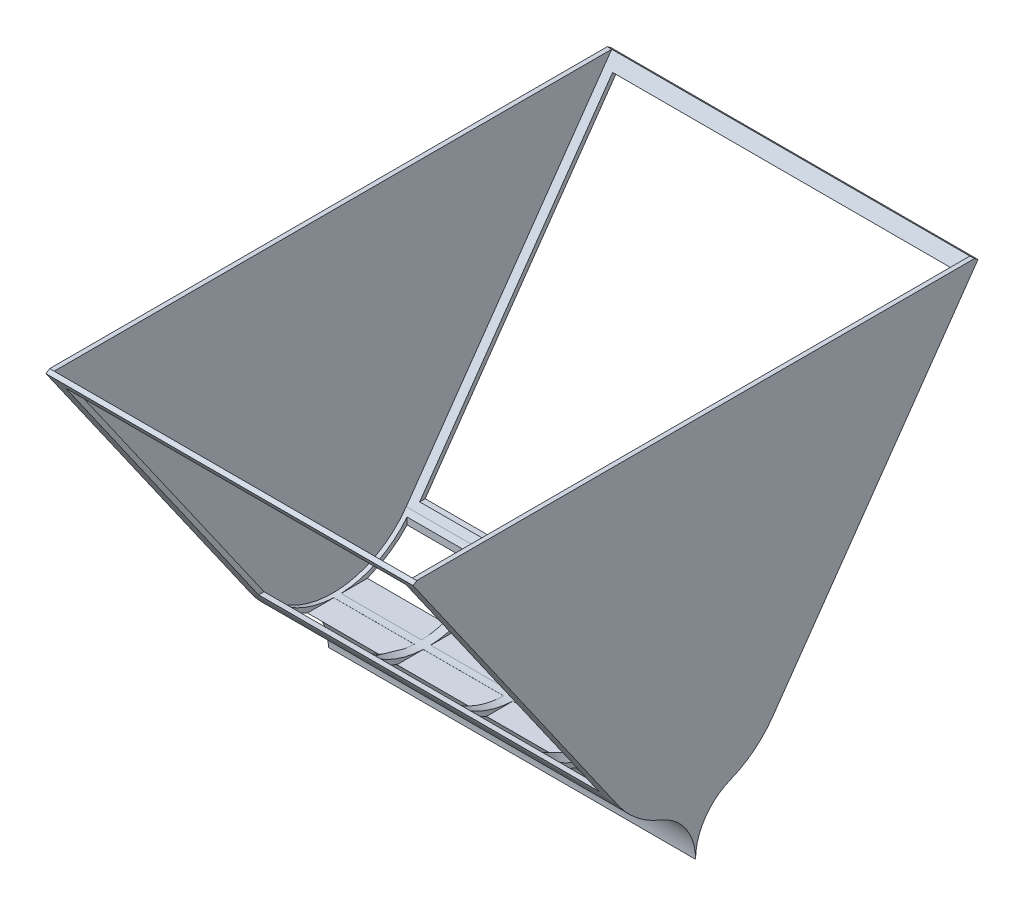
SolidWorks part; units mm, degrees
note: The reader was unsure of these and kept them because the rebuilt part matched: shared geometry of "Sketch4<3>".
ref_plane "Front Plane" through (0, 0, 0) normal (0, 0, 1) x (1, 0, 0)
ref_plane "Top Plane" through (0, 0, 0) normal (0, 1, 0) x (1, 0, 0)
ref_plane "Right Plane" through (0, 0, 0) normal (1, 0, 0) x (0, 0, -1)
sketch "Sketch1" plane through (0, 0, 0) normal (1, 0, 0) x (0, 0, -1)
  line L0 (-16.383, -11.4715) -> (-62.2692, 54.0606)
  line L1 (16.383, -11.4715) -> (62.2692, 54.0606)
  line L2 (-17.2022, -12.0451) -> (-63.0883, 53.4871)
  line L3 (17.2022, -12.0451) -> (63.0883, 53.4871)
  line L4 (0, -21) -> (0, -31) construction
  line L5 (16.383, -11.4715) -> (62.2692, 54.0606) construction
  line L6 (-62.2692, 54.0606) -> (-63.0883, 53.4871)
  line L7 (62.2692, 54.0606) -> (63.0883, 53.4871)
  arc A0 (-16.383, -11.4715) -> (16.383, -11.4715) centre (0, 0) ccw
  arc A1 (-17.2022, -12.0451) -> (17.2022, -12.0451) centre (0, 0) ccw
  arc A2 (7.7889, -19.5021) -> (0, -31) centre (12.381, -31) ccw
  arc A3 (0, -31) -> (-7.7889, -19.5021) centre (-12.381, -31) ccw
  dimension "D3" = 20
  dimension "D2" = 10
  dimension "D4" = 80
  dimension "D5" = 70
  dimension "D1" = 1
extrude "Boss-Extrude1" add sketch "Sketch1" along normal blind 80 contours L2 A1 L3 L7 L1 A0 L0 L6 | A3 A2 A1
sketch "Sketch2" plane through (0, 0, 0) normal (0, 0, 1) x (1, 0, 0)
  line L0 (78, 51.4871) -> (2, 51.4871)
  line L1 (2, 51.4871) -> (2, -10.0451)
  line L2 (2, -10.0451) -> (78, -10.0451)
  line L3 (78, -10.0451) -> (78, 51.4871)
  line L4 (0, 53.4871) -> (0, -12.0451)
  line L5 (80, 53.4871) -> (0, 53.4871)
  line L6 (80, -12.0451) -> (80, 53.4871)
  line L7 (0, -12.0451) -> (80, -12.0451)
  line L8 (0, 53.4871) -> (0, -12.0451)
  line L9 (80, 53.4871) -> (0, 53.4871)
  line L10 (80, -12.0451) -> (80, 53.4871)
  line L11 (0, -12.0451) -> (80, -12.0451)
  line L12 (0, -12.0451) -> (0, -19.5021)
  line L13 (80, -12.0451) -> (0, -12.0451)
  line L14 (80, -19.5021) -> (80, -12.0451)
  line L15 (0, -19.5021) -> (80, -19.5021)
  line L16 (0, -12.0451) -> (0, -19.5021)
  line L17 (80, -12.0451) -> (0, -12.0451)
  line L18 (80, -19.5021) -> (80, -12.0451)
  line L19 (0, -19.5021) -> (80, -19.5021)
  dimension "D1" = 0
  dimension "D2" = 0
  dimension "D3" = 2
extrude "Cut-Extrude1" cut sketch "Sketch2" against normal through all both and the other way through all contours L2 L3 L0 L1
sketch "Sketch3" plane through (0, 0, 0) normal (0, 1, 0) x (1, 0, 0)
  line L0 (80, 0) -> (0, 0) construction
  line L1 (80, 0) -> (0, 0)
  line L2 (40, -16.383) -> (40, 16.383)
  line L3 (40, 16.383) -> (0, -16.383)
  line L4 (0, 16.383) -> (0, -16.383)
  line L5 (0, -16.383) -> (80, -16.383)
  line L6 (80, -16.383) -> (80, 16.383)
  line L7 (80, 16.383) -> (0, 16.383)
  line L8 (0, 16.383) -> (0, -16.383)
  line L9 (0, -16.383) -> (80, -16.383)
  line L10 (80, -16.383) -> (80, 16.383)
  line L11 (80, 16.383) -> (0, 16.383)
  line L12 (0, 16.383) -> (40, -16.383)
  line L13 (40, -16.383) -> (80, 16.383)
  line L14 (0, 7.7889) -> (0, 0)
  line L15 (80, 7.7889) -> (0, 7.7889)
  line L16 (80, 0) -> (80, 7.7889)
  line L17 (0, 0) -> (80, 0)
  line L18 (0, 7.7889) -> (0, 0)
  line L19 (80, 7.7889) -> (0, 7.7889)
  line L20 (80, 0) -> (80, 7.7889)
  line L21 (0, 0) -> (80, 0)
  line L22 (0, 0) -> (0, -7.7889)
  line L23 (80, 0) -> (0, 0)
  line L24 (80, -7.7889) -> (80, 0)
  line L25 (0, -7.7889) -> (80, -7.7889)
  line L26 (0, 0) -> (0, -7.7889)
  line L27 (80, 0) -> (0, 0)
  line L28 (80, -7.7889) -> (80, 0)
  line L29 (0, -7.7889) -> (80, -7.7889)
  line L30 (40, 16.383) -> (80, -16.383)
  line L31 (60, 0) -> (60, -16.383)
  line L32 (60, -16.383) -> (60, 16.383)
  line L33 (20, 0) -> (20, 16.383)
  line L34 (20, 16.383) -> (20, -16.383)
  line L36 (1, -15.5639) -> (19, -15.5639)
  line L37 (1, -15.5639) -> (1, -0.8192)
  line L38 (1, -0.8192) -> (19, -0.8192)
  line L39 (19, -15.5639) -> (19, -0.8192)
  line L40 (1, 15.5639) -> (19, 15.5639)
  line L41 (1, 15.5639) -> (1, 0.8192)
  line L42 (1, 0.8192) -> (19, 0.8192)
  line L43 (19, 15.5639) -> (19, 0.8192)
  line L44 (21, 15.5639) -> (39, 15.5639)
  line L45 (21, 15.5639) -> (21, 0.8192)
  line L46 (21, 0.8192) -> (39, 0.8192)
  line L47 (39, 15.5639) -> (39, 0.8192)
  line L48 (21, -15.5639) -> (39, -15.5639)
  line L49 (21, -15.5639) -> (21, -0.8192)
  line L50 (21, -0.8192) -> (39, -0.8192)
  line L51 (39, -15.5639) -> (39, -0.8192)
  line L52 (41, -15.5639) -> (59, -15.5639)
  line L53 (41, -15.5639) -> (41, -0.8192)
  line L54 (41, -0.8192) -> (59, -0.8192)
  line L55 (59, -15.5639) -> (59, -0.8192)
  line L56 (41, 0.8192) -> (59, 0.8192)
  line L57 (41, 0.8192) -> (41, 15.5639)
  line L58 (41, 15.5639) -> (59, 15.5639)
  line L59 (59, 0.8192) -> (59, 15.5639)
  line L60 (61, -15.5639) -> (79, -15.5639)
  line L61 (61, -15.5639) -> (61, -0.8192)
  line L62 (61, -0.8192) -> (79, -0.8192)
  line L63 (79, -15.5639) -> (79, -0.8192)
  line L64 (61, 0.8192) -> (79, 0.8192)
  line L65 (61, 0.8192) -> (61, 15.5639)
  line L66 (61, 15.5639) -> (79, 15.5639)
  line L67 (79, 0.8192) -> (79, 15.5639)
  point P54 (0, 0)
  point P55 (0, 0)
  dimension "D4" = 1
  dimension "D5" = 1
  dimension "D1" = 0
  dimension "D2" = 0
  dimension "D3" = 0
extrude "Cut-Extrude2" cut sketch "Sketch3" against normal up to vertex (20 mm away) contours L37 L3 L29 | L38 L37 L29 L3 | L36 L39 L29 L3 | L29 L39 L3 | L41 L42 L12 L19 | L12 L41 L19 | L43 L40 L12 L19 | L43 L19 L12 | L19 L45 L3 | L44 L45 L19 L3 | L47 L19 L3 L46 | L47 L3 L19 | L29 L51 L50 L12 | L49 L29 L12 | L49 L48 L12 L29 | L12 L51 L29 | L52 L55 L29 L13 | L53 L13 L29 | L54 L53 L29 L13 | L29 L55 L13 | L57 L56 L30 L19 | L57 L19 L30 | L19 L59 L58 L30 | L30 L59 L19 | L66 L65 L19 L13 | L65 L13 L19 | L64 L67 L19 L13 | L19 L67 L13 | L29 L63 L62 L30 | L61 L29 L30 | L61 L60 L30 L29 | L30 L63 L29
sketch "Sketch4" plane through (80, 0, 0) normal (1, 0, 0) x (0, 0, -1)
  line L0 (-62.2692, 54.0606) -> (62.2692, 54.0606)
  line L6 (-63.0883, 53.4871) -> (-17.2022, -12.0451)
  line L7 (17.2022, -12.0451) -> (63.0883, 53.4871)
  line L8 (63.0883, 53.4871) -> (62.2692, 54.0606)
  line L9 (62.2692, 54.0606) -> (16.383, -11.4715)
  line L10 (-16.383, -11.4715) -> (-62.2692, 54.0606)
  line L11 (-62.2692, 54.0606) -> (-63.0883, 53.4871)
  line L12 (-63.0883, 53.4871) -> (-17.2022, -12.0451)
  line L13 (17.2022, -12.0451) -> (63.0883, 53.4871)
  line L14 (63.0883, 53.4871) -> (62.2692, 54.0606)
  line L15 (62.2692, 54.0606) -> (16.383, -11.4715)
  line L16 (-16.383, -11.4715) -> (-62.2692, 54.0606)
  line L17 (-62.2692, 54.0606) -> (-63.0883, 53.4871)
  arc A5 (-17.2022, -12.0451) -> (-7.7889, -19.5021) centre (0, 0) ccw
  arc A6 (0, -31) -> (-7.7889, -19.5021) centre (-12.381, -31) ccw
  arc A7 (7.7889, -19.5021) -> (0, -31) centre (12.381, -31) ccw
  arc A8 (7.7889, -19.5021) -> (17.2022, -12.0451) centre (0, 0) ccw
  arc A9 (-16.383, -11.4715) -> (16.383, -11.4715) centre (0, 0) ccw
  arc A10 (-17.2022, -12.0451) -> (-7.7889, -19.5021) centre (0, 0) ccw
  arc A11 (0, -31) -> (-7.7889, -19.5021) centre (-12.381, -31) ccw
  arc A12 (7.7889, -19.5021) -> (0, -31) centre (12.381, -31) ccw
  arc A13 (7.7889, -19.5021) -> (17.2022, -12.0451) centre (0, 0) ccw
  arc A14 (-16.383, -11.4715) -> (16.383, -11.4715) centre (0, 0) ccw
  line M12 (-63.0883, 53.4871) -> (-17.2022, -12.0451)
  arc M13 (-17.2022, -12.0451) -> (-7.7889, -19.5021) centre (0, 0) ccw
  arc M14 (-7.7889, -19.5021) -> (0, -31) centre (-12.381, -31) cw
  arc M15 (0, -31) -> (7.7889, -19.5021) centre (12.381, -31) cw
  arc M16 (7.7889, -19.5021) -> (17.2022, -12.0451) centre (0, 0) ccw
  line M17 (17.2022, -12.0451) -> (63.0883, 53.4871)
  line M18 (63.0883, 53.4871) -> (62.2692, 54.0606)
  line M19 (62.2692, 54.0606) -> (16.383, -11.4715)
  arc M20 (16.383, -11.4715) -> (-16.383, -11.4715) centre (0, 0) cw
  line M21 (-16.383, -11.4715) -> (-62.2692, 54.0606)
  line M22 (-62.2692, 54.0606) -> (-63.0883, 53.4871)
  dimension "D1" = 0
extrude "Boss-Extrude2" add sketch "Sketch4" along normal blind 1 contours L0 M21 M20 M19 | M22 M12 M13 M14 M15 M16 M17 M18 M19 M20 M21
extrude "Boss-Extrude3" add sketch "Sketch4<3>" against normal blind 1 from surface at -80 contours L0 M21 M20 M19 | M22 M12 M13 M14 M15 M16 M17 M18 M19 M20 M21 starting at face at (0, 8.2313, 0)
sketch "Sketch4<3>" plane through (80, 0, 0) normal (1, 0, 0) x (0, 0, -1) same geometry as "Sketch4"
